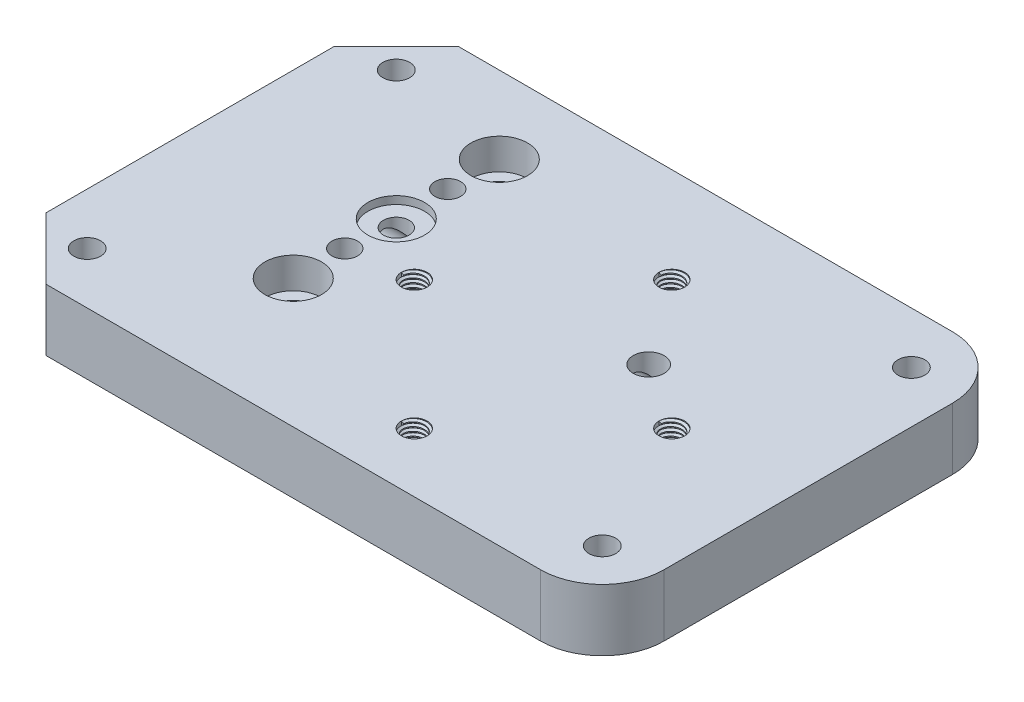
SolidWorks part; units mm, degrees
ref_plane "Front Plane" through (0, 0, 0) normal (0, 0, 1) x (1, 0, 0)
ref_plane "Top Plane" through (0, 0, 0) normal (0, 1, 0) x (1, 0, 0)
ref_plane "Right Plane" through (0, 0, 0) normal (1, 0, 0) x (0, 0, -1)
sketch "Sketch1" plane through (0, 0, 0) normal (0, 1, 0) x (1, 0, 0)
  line L1 (0, 0) -> (120, 0)
  line L2 (0, 0) -> (0, 80)
  line L3 (0, 80) -> (120, 80)
  line L4 (120, 0) -> (120, 80)
  dimension "D1" = 120
  dimension "D2" = 80
extrude "Boss-Extrude1" add sketch "Sketch1" along normal blind 12
sketch "Sketch2" plane through (0, 12, 0) normal (0, 1, 0) x (1, 0, 0)
  line L1 (0, 0) -> (120, 0) construction
  line L2 (12, 0) -> (0, 0)
  line L3 (0, 0) -> (0, 12)
  line L4 (0, 80) -> (0, 0) construction
  line L5 (12, 0) -> (0, 12)
  line L6 (120, 80) -> (0, 80) construction
  line L7 (12, 80) -> (0, 80)
  line L8 (0, 68) -> (12, 80)
  line L9 (0, 68) -> (0, 80)
  dimension "D1" = 12
  dimension "D2" = 12
  dimension "D3" = 12
  dimension "D4" = 12
extrude "Cut-Extrude1" cut sketch "Sketch2" against normal through all
sketch "Sketch3" plane through (0, 12, 0) normal (0, 1, 0) x (1, 0, 0)
  line L0 (0, 68) -> (0, 12) construction
  line L1 (120, 80) -> (12, 80) construction
  line L2 (12, 0) -> (120, 0) construction
  line L3 (120, 0) -> (120, 80) construction
  circle A0 centre (10, 70) radius 2.6
  circle A1 centre (10, 10) radius 2.6
  circle A2 centre (110, 10) radius 2.6
  circle A3 centre (110, 70) radius 2.6
  dimension "D3" = 5.2
  dimension "D6" = 5.2
  dimension "D7" = 5.2
  dimension "D8" = 10
  dimension "D10" = 5.2
  dimension "D1" = 10
  dimension "D2" = 10
  dimension "D4" = 10
  dimension "D5" = 10
  dimension "D9" = 10
  dimension "D11" = 10
  dimension "D12" = 10
extrude "Cut-Extrude2" cut sketch "Sketch3" against normal through all
fillet "Fillet1" radius 12 2 edges at (120, 6, 0) (120, 6, -80)
sketch "Sketch4" plane through (0, 12, 0) normal (0, 1, 0) x (1, 0, 0)
  circle A1 centre (97, 36.5) radius 2.5
  circle A2 centre (72, 61.5) radius 2.5
  circle A3 centre (47, 36.5) radius 2.5
  circle A4 centre (72, 11.5) radius 2.5
  dimension "D2" = 5
  dimension "D1" = 5
  dimension "D3" = 5
  dimension "D4" = 5
extrude "Cut-Extrude3" cut sketch "Sketch4" against normal through all
thread "Thread1" pitch 0.8 method extrude profile "Thread Profile1" start angle 0, offset 0, length 10, pitch 0.8, diameter 5
ref_plane "Plane1" through (69.5, 12, -11.5) normal (0, 0, 1) x (-1, 0, 0)
sketch "Thread Profile1" plane through (69.5, 12, -11.5) normal (0, 0, 1) x (-1, 0, 0)
  line L0 (0, 0) -> (0, 0.8) construction
  line L11 (0, 0) -> (0, 0.7)
  line L12 (0, 0.7) -> (-0.433, 0.45)
  line L13 (-0.433, 0.45) -> (-0.433, 0.25)
  line L15 (-0.433, 0.25) -> (0, 0)
  line L17 (-0.433, 0.35) -> (0, 0.35) construction
  point P2 (0, 0)
  dimension "Pitch" = 0.8
  dimension "Profile_Angle" = 60
  dimension "Profile_Land" = 0.2
  dimension "Profile_Height" = 0.433
thread "Thread2" pitch 0.8 method extrude profile "Thread Profile2" start angle 0, offset 0, length 10, pitch 0.8, diameter 5
ref_plane "Plane2" through (94.5, 12, -36.5) normal (0, 0, 1) x (-1, 0, 0)
sketch "Thread Profile2" plane through (94.5, 12, -36.5) normal (0, 0, 1) x (-1, 0, 0)
  line L0 (0, 0) -> (0, 0.8) construction
  line L11 (0, 0) -> (0, 0.7)
  line L12 (0, 0.7) -> (-0.433, 0.45)
  line L13 (-0.433, 0.45) -> (-0.433, 0.25)
  line L15 (-0.433, 0.25) -> (0, 0)
  line L17 (-0.433, 0.35) -> (0, 0.35) construction
  point P2 (0, 0)
  dimension "Pitch" = 0.8
  dimension "Profile_Angle" = 60
  dimension "Profile_Land" = 0.2
  dimension "Profile_Height" = 0.433
thread "Thread3" pitch 0.8 method extrude profile "Thread Profile3" start angle 0, offset 0, length 10, pitch 0.8, diameter 5
ref_plane "Plane3" through (69.5, 12, -61.5) normal (0, 0, 1) x (-1, 0, 0)
sketch "Thread Profile3" plane through (69.5, 12, -61.5) normal (0, 0, 1) x (-1, 0, 0)
  line L0 (0, 0) -> (0, 0.8) construction
  line L11 (0, 0) -> (0, 0.7)
  line L12 (0, 0.7) -> (-0.433, 0.45)
  line L13 (-0.433, 0.45) -> (-0.433, 0.25)
  line L15 (-0.433, 0.25) -> (0, 0)
  line L17 (-0.433, 0.35) -> (0, 0.35) construction
  point P2 (0, 0)
  dimension "Pitch" = 0.8
  dimension "Profile_Angle" = 60
  dimension "Profile_Land" = 0.2
  dimension "Profile_Height" = 0.433
thread "Thread4" pitch 0.8 method extrude profile "Thread Profile4" start angle 0, offset 0, length 10, pitch 0.8, diameter 5
ref_plane "Plane4" through (44.5, 12, -36.5) normal (0, 0, 1) x (-1, 0, 0)
sketch "Thread Profile4" plane through (44.5, 12, -36.5) normal (0, 0, 1) x (-1, 0, 0)
  line L0 (0, 0) -> (0, 0.8) construction
  line L11 (0, 0) -> (0, 0.7)
  line L12 (0, 0.7) -> (-0.433, 0.45)
  line L13 (-0.433, 0.45) -> (-0.433, 0.25)
  line L15 (-0.433, 0.25) -> (0, 0)
  line L17 (-0.433, 0.35) -> (0, 0.35) construction
  point P2 (0, 0)
  dimension "Pitch" = 0.8
  dimension "Profile_Angle" = 60
  dimension "Profile_Land" = 0.2
  dimension "Profile_Height" = 0.433
sketch "Sketch5" plane through (0, 0, 0) normal (-1, 0, 0) x (0, 0, 1)
  line L0 (-80, 0) -> (-80, 12) construction
  line L1 (-68, 12) -> (-12, 12) construction
  circle A0 centre (-45, 6) radius 3
  dimension "D2" = 6
  dimension "D1" = 35
  dimension "D3" = 6
extrude "Cut-Extrude4" cut sketch "Sketch5" against normal blind 88
sketch "Sketch6" plane through (0, 0, 0) normal (-1, 0, 0) x (0, 0, 1)
  circle A0 centre (-45, 6) radius 4
  dimension "D1" = 8
extrude "Cut-Extrude5" cut sketch "Sketch6" against normal blind 15
thread "Thread5" pitch 1 method extrude profile "Thread Profile5" start angle 0, offset 0, length 13, pitch 1, diameter 8
ref_plane "Plane5" through (0, 6, -49) normal (0, -1, 0) x (0, 0, -1)
sketch "Thread Profile5" plane through (0, 6, -49) normal (0, -1, 0) x (0, 0, -1)
  line L0 (0, 0) -> (0, 1) construction
  line L11 (0, 0) -> (0, 0.875)
  line L12 (0, 0.875) -> (-0.5413, 0.5625)
  line L13 (-0.5413, 0.5625) -> (-0.5413, 0.3125)
  line L15 (-0.5413, 0.3125) -> (0, 0)
  line L17 (-0.5413, 0.4375) -> (0, 0.4375) construction
  point P2 (0, 0)
  dimension "Pitch" = 1
  dimension "Profile_Angle" = 60
  dimension "Profile_Land" = 0.25
  dimension "Profile_Height" = 0.5413
sketch "Sketch10" plane through (0, 12, 0) normal (0, 1, 0) x (1, 0, 0)
  line L0 (108, 80) -> (12, 80) construction
  line L1 (0, 68) -> (0, 12) construction
  circle A0 centre (35, 45) radius 5.5
  dimension "D2" = 11
  dimension "D1" = 35
  dimension "D3" = 35
extrude "Cut-Extrude6" cut sketch "Sketch10" against normal blind 1.5
sketch "Sketch11" plane through (0, 10.5, 0) normal (0, 1, 0) x (1, 0, 0)
  circle A0 centre (35, 45) radius 2.5
  dimension "D1" = 5
extrude "Cut-Extrude7" cut sketch "Sketch11" against normal blind 5
sketch "Sketch12" plane through (0, 12, 0) normal (0, 1, 0) x (1, 0, 0)
  line L0 (0, 68) -> (0, 12) construction
  line L1 (0, 68) -> (0, 12) construction
  circle A0 centre (35, 65) radius 3.25
  circle A1 centre (35, 45) radius 2.5 construction
  circle A2 centre (35, 25) radius 3.25
  dimension "D3" = 6.5
  dimension "D5" = 20
  dimension "D6" = 6.5
  dimension "D1" = 35
  dimension "D2" = 35
  dimension "D4" = 35
extrude "Cut-Extrude8" cut sketch "Sketch12" against normal through all
sketch "Sketch14" plane through (0, 12, 0) normal (0, 1, 0) x (1, 0, 0)
  line L0 (0, 68) -> (0, 12) construction
  line L1 (0, 68) -> (0, 12) construction
  circle A0 centre (35, 35) radius 2.5
  circle A1 centre (35, 55) radius 2.5
  circle A2 centre (35, 45) radius 2.5 construction
  dimension "D4" = 5
  dimension "D6" = 5
  dimension "D1" = 35
  dimension "D2" = 35
  dimension "D3" = 10
  dimension "D5" = 10
extrude "Cut-Extrude9" cut sketch "Sketch14" against normal through all
sketch "Sketch15" plane through (0, 12, 0) normal (0, 1, 0) x (1, 0, 0)
  circle A0 centre (35, 25) radius 5.5
  circle A1 centre (35, 65) radius 5.5
  dimension "D1" = 11
  dimension "D2" = 11
extrude "Cut-Extrude10" cut sketch "Sketch15" against normal blind 6
sketch "Sketch16" plane through (0, 12, 0) normal (0, 1, 0) x (1, 0, 0)
  line L0 (108, 80) -> (12, 80) construction
  line L1 (0, 68) -> (0, 12) construction
  circle A0 centre (84, 45) radius 3
  dimension "D3" = 6
  dimension "D1" = 35
  dimension "D2" = 84
extrude "Cut-Extrude11" cut sketch "Sketch16" against normal blind 6
